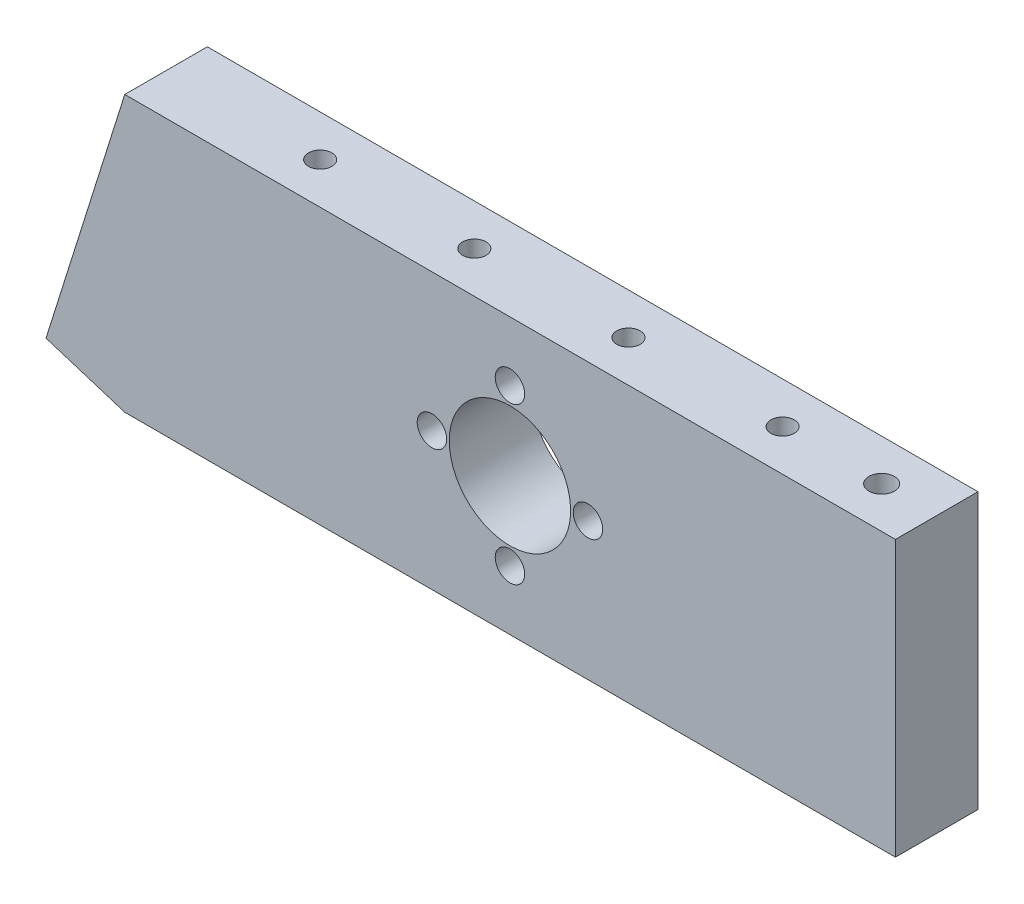
SolidWorks part; units mm, degrees
material "PE High Density"
ref_plane "Front Plane" through (0, 0, 0) normal (0, 0, 1) x (1, 0, 0)
ref_plane "Top Plane" through (0, 0, 0) normal (0, 1, 0) x (1, 0, 0)
ref_plane "Right Plane" through (0, 0, 0) normal (1, 0, 0) x (0, 0, -1)
sketch "Sketch1" plane through (0, 0, 0) normal (0, 0, 1) x (1, 0, 0)
  line L1 (-44.433, 15.875) -> (44.467, 15.875)
  line L3 (-44.433, -15.875) -> (44.467, -15.875)
  line L5 (18.5214, 15.875) -> (18.5214, -15.875) construction
  line L6 (0, 0) -> (44.467, 0) construction
  line L10 (-44.433, 15.875) -> (-53.5192, -13.0175)
  line L12 (0.017, -15.875) -> (0.017, 75.0464) construction
  line L13 (0.017, -15.875) -> (147.1451, -15.875) construction
  line L14 (-44.433, -15.875) -> (-44.433, 15.875) construction
  line L15 (44.467, 15.875) -> (44.467, -15.875)
  line L17 (-44.433, -15.875) -> (-53.5192, -13.0175)
  line L22 (-90.4237, 20.5209) -> (-90.4237, -9.9591) construction
  line L25 (-44.433, 15.875) -> (-28.8763, 10.9827) construction
  circle A2 centre (0, 9) radius 1.7 construction
  arc A8 (-5.3578, -2.967) -> (-5.3172, -2.9531) centre (-6.35, 0) ccw construction
  circle A16 centre (0, 0) radius 7 construction
  circle A17 centre (0, 0) radius 9 construction
  circle A20 centre (9, 0) radius 1.7 construction
  circle A21 centre (0, -9) radius 1.7 construction
  circle A22 centre (-9, 0) radius 1.7 construction
  circle A23 centre (-90.4237, -2.6566) radius 2.2479 construction
  circle A24 centre (-90.4237, 13.2184) radius 2.2479 construction
  circle A27 centre (0, -9) radius 1.7
  circle A28 centre (-9, 0) radius 1.7
  circle A29 centre (0, 9) radius 1.7
  circle A30 centre (9, 0) radius 1.7
  circle A43 centre (0, 0) radius 7
  point P0 (0, 0)
  point P27 (0, 0)
  point P44 (0, 0)
  dimension "D5" = 14
  dimension "D12" = 18.0001
  dimension "D3" = 3.4
  dimension "D20" = 4.4958
  dimension "D21" = 4.4958
  dimension "D8" = 88.9
  dimension "D17" = 88.9
  dimension "D2" = 90
  dimension "D10" = 31.75
  dimension "D4" = 90
  dimension "D9" = 90
  dimension "D11" = 44.467
  dimension "D13" = 90
  dimension "D15" = 30.48
  dimension "D16" = 7.3025
  dimension "D18" = 7.3025
  dimension "D22" = 90
  dimension "D14" = 9.525
  dimension "D6" = 4
extrude "Boss-Extrude1" add sketch "Sketch1" along normal blind 9.525
hole_wizard "Tap Drill for #6-32 Tap1" positions "Sketch11" profile "Sketch12" hole size "#6-32" standard "ANSI Inch"
sketch "Sketch11" plane through (0, -15.875, 0) normal (0, -1, 0) x (-1, 0, 0)
  line L0 (-44.467, -9.525) -> (-44.467, 0) construction
  line L1 (44.433, -9.525) -> (-44.467, -9.525) construction
  point P0 (-26.687, -4.7625)
  dimension "D1" = 17.78
  dimension "D2" = 4.7625
sketch "Sketch12" plane through (26.687, -15.875, 4.7625) normal (1, 0, 0) x (0, 0, -1)
  line L0 (0, 0) -> (0, 13.5127)
  line L1 (0, 13.5127) -> (1.3525, 12.7)
  line L2 (1.3525, 12.7) -> (1.3525, 0)
  line L5 (1.3525, 0) -> (0, 0)
  line L10 (0, 13.5127) -> (-1.3526, 12.7) construction
  line L11 (0, -6.35) -> (0, 107.95) construction
  dimension "Hole Dia." = 2.7051
  dimension "Hole Depth" = 12.7
  dimension "Drill Angle" = 118
pattern_linear "LPattern1" count 4 spacing 17.78 along (-1, 0, 0) of "Tap Drill for #6-32 Tap1"
mirror "Mirror8" about plane through (0, 0, 0) normal (0, 1, 0) of "Tap Drill for #6-32 Tap1", "LPattern1"
sketch "Sketch13" plane through (0, -15.875, 0) normal (0, -1, 0) x (1, 0, 0)
  line L0 (38.117, 9.525) -> (38.117, 0) construction
  line L1 (-44.433, 9.525) -> (44.467, 9.525) construction
  line L2 (-44.433, 0) -> (44.467, 0) construction
  line L3 (44.467, 9.525) -> (44.467, 0) construction
  circle A0 centre (38.117, 4.7625) radius 1.4732
  dimension "D2" = 2.9464
  dimension "D1" = 6.35
extrude "Cut-Extrude1" cut sketch "Sketch13" against normal blind 12.7
mirror "Mirror9" about plane through (0, 0, 0) normal (0, 1, 0) of "Cut-Extrude1"
equation "\"Plate Screw Hole Diameter\"= 0.116in"
equation "\"Plate Width\" = 3.5in"
equation "\"Plate Thickness\" = 0.375in"
equation "\"Num holes\" = 4"
equation "\"Plate Height\" = 1.25in"
equation "\"D1@Sketch11\"=\"Plate Width\" / ( \"Num holes\" + 1)"
equation "\"D2@Sketch11\"=\"Plate Thickness\"/2"
equation "\"D3@LPattern1\"=\"Plate Width\" / ( \"Num holes\"  + 1 )"
equation "\"Top Plate Width\" = 4.5in"
equation "\"D8@Sketch1\"=\"Plate Width\""
equation "\"Plate Clearance Hole Diameter\" = 0.125in"
equation "\"Plate Tap Hole Diameter\" = 0.116in"
equation "\"Bottom Plate Length\" = 6.5in"
equation "\"Number Eight Clearance Size\" = 0.177in"
equation "\"back_brace_height_offset\"=0.35"
equation "\"D2@Sketch13\"=\"Plate Tap Hole Diameter\""
equation "\"D17@Sketch1\"=\"Plate Width\""
equation "\"D10@Sketch1\"=\"Plate Height\""
